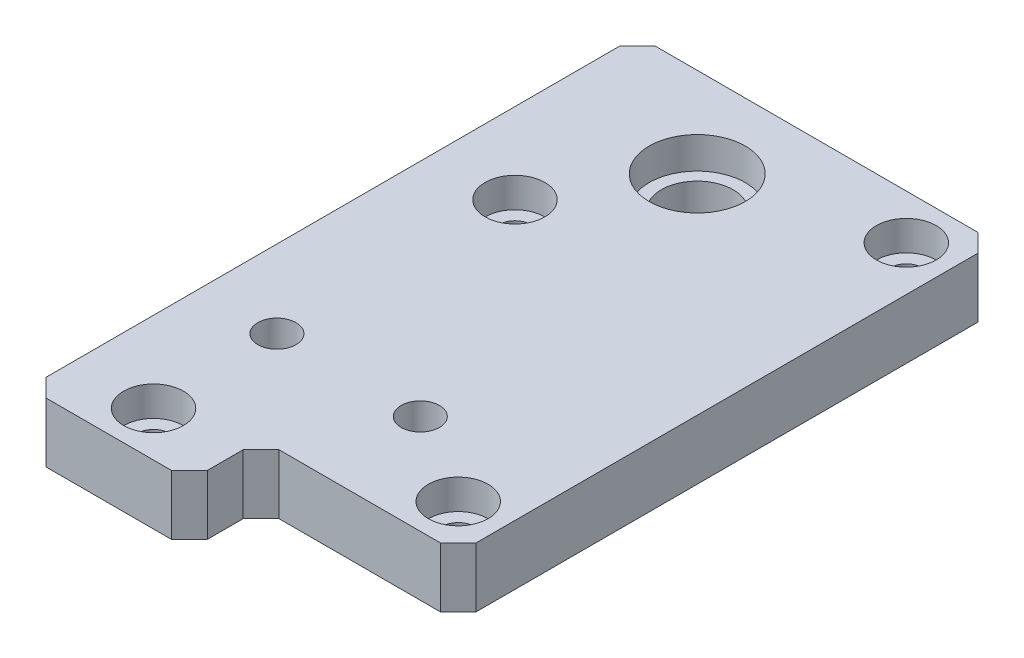
SolidWorks part; units mm, degrees
material "PET"
ref_plane "Front Plane" through (0, 0, 0) normal (0, 0, 1) x (1, 0, 0)
ref_plane "Top Plane" through (0, 0, 0) normal (0, 1, 0) x (1, 0, 0)
ref_plane "Right Plane" through (0, 0, 0) normal (1, 0, 0) x (0, 0, -1)
sketch "Sketch1" plane through (0, 0, 0) normal (0, 1, 0) x (1, 0, 0)
  line L1 (2, -45) -> (35, -45)
  line L3 (-25, 45) -> (35, 45)
  line L4 (35, -45) -> (35, 45)
  line L5 (-25, -57) -> (2, -57)
  line L6 (2, -57) -> (2, -45)
  line L7 (-25, 45) -> (-25, -57)
  point P0 (0, 0)
  dimension "D1" = 60
  dimension "D2" = 90
  dimension "D3" = 35
  dimension "D4" = 45
  dimension "D5" = 12
  dimension "D6" = 27
extrude "Boss-Extrude1" add sketch "Sketch1" along normal blind 10
sketch "Sketch4" plane through (0, 10, 0) normal (0, 1, 0) x (1, 0, 0)
  line L3 (35, -45) -> (35, 45) construction
  line L4 (2, -45) -> (35, -45) construction
  line L5 (35, 45) -> (-25, 45) construction
  line L6 (-25, -57) -> (2, -57) construction
  point P4 (27.5, 37.5)
  point P6 (27.5, -37.5)
  point P23 (-11.5, 11)
  point P25 (-11.5, -49.5)
  point P32 (-11.5, -57)
  dimension "D1" = 7.5
  dimension "D2" = 49.5
  dimension "D3" = 7.5
  dimension "D4" = 7.5
  dimension "D5" = 11
hole_wizard "CBORE for M5 SHCS1" positions "Sketch4" profile "Sketch3" counterbore size "M5" standard "ANSI Metric" end condition through all
sketch "Sketch3" plane through (27.5, 10, -37.5) normal (1, 0, 0) x (0, 0, 1)
  line L0 (0, 0) -> (0, 10)
  line L1 (0, 10) -> (2.75, 10)
  line L3 (2.75, 10) -> (2.75, 5)
  line L4 (2.75, 5) -> (5, 5)
  line L5 (5, 5) -> (5, 0)
  line L7 (5, 0) -> (0, 0)
  line L11 (0, -6.35) -> (0, 107.95) construction
  dimension "Thru Hole Dia." = 5.5
  dimension "Thru Hole Depth" = 10
  dimension "C'Bore Dia." = 10
  dimension "C'Bore Depth" = 5
sketch "Sketch7" plane through (0, 10, 0) normal (0, 1, 0) x (1, 0, 0)
  line L0 (35, 45) -> (-25, 45) construction
  point P0 (0, 30)
  dimension "D1" = 15
hole_wizard "Ø1.0mm Dowel Hole1" positions "Sketch7" profile "Sketch6" hole size "Ø1.0" standard "ANSI Metric"
sketch "Sketch6" plane through (0, 10, -30) normal (1, 0, 0) x (0, 0, 1)
  line L0 (0, 0) -> (0, 5.3)
  line L1 (0, 5.3) -> (8.05, 5.3)
  line L2 (8.05, 5.3) -> (8.05, 0)
  line L5 (8.05, 0) -> (0, 0)
  line L10 (0, 5.3) -> (-8.05, 5.3) construction
  line L11 (0, -6.35) -> (0, 107.95) construction
  dimension "Hole Dia." = 16.1
  dimension "Hole Depth" = 5.3
  dimension "Drill Angle" = 180
sketch "Sketch13" plane through (0, 4.7, 0) normal (0, 1, 0) x (1, 0, 0)
  point P0 (0, 30)
hole_wizard "Ø1.0mm Dowel Hole3" positions "Sketch13" profile "Sketch12" hole size "Ø1.0" standard "ANSI Metric" end condition through all
sketch "Sketch12" plane through (0, 4.7, -30) normal (1, 0, 0) x (0, 0, 1)
  line L0 (0, 0) -> (0, 4.7)
  line L1 (0, 4.7) -> (6, 4.7)
  line L2 (6, 4.7) -> (6, 0)
  line L5 (6, 0) -> (0, 0)
  line L11 (0, -6.35) -> (0, 107.95) construction
  dimension "Thru Hole Dia." = 12
  dimension "Thru Hole Depth" = 4.7
sketch "Sketch14" plane through (0, 10, 0) normal (0, 1, 0) x (1, 0, 0)
  circle A2 centre (12, -28.35) radius 3.2
  circle A3 centre (-12, -28.35) radius 3.2
  dimension "D5" = 6.4
  dimension "D6" = 6.4
  dimension "D1" = 28.35
  dimension "D2" = 12
  dimension "D3" = 12
  dimension "D4" = 28.35
extrude "Cut-Extrude1" cut sketch "Sketch14" against normal through all
chamfer "Chamfer1" distance 3 angle 45 6 edges at (35, 5, -45) (35, 5, 45) (2, 5, 45) (2, 5, 57) (-25, 5, 57) (-25, 5, -45)
equation "\"D4@Sketch14\"=\"D1@Sketch14\""
equation "\"D4@Sketch1\"=0.5*\"D2@Sketch1\""
